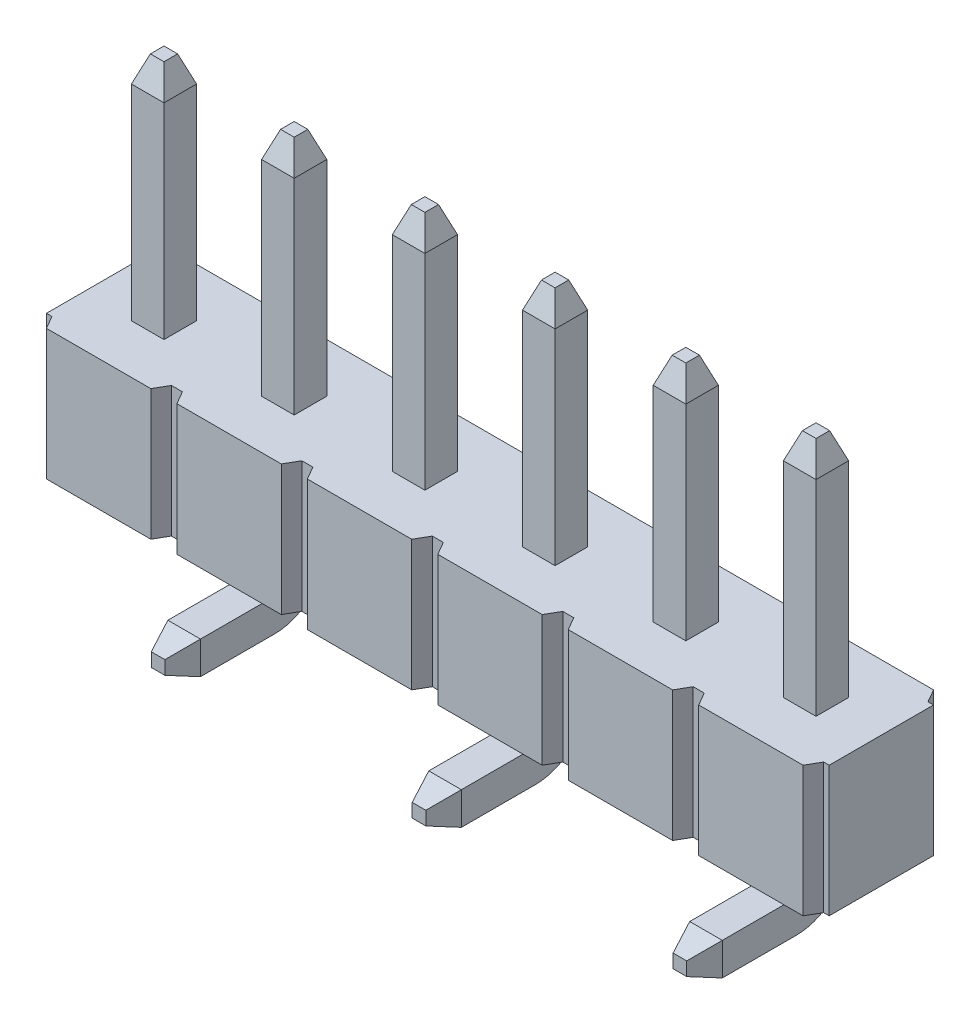
SolidWorks part; units mm, degrees
note: '?' marks a value the reader was unsure of.
ref_plane "Front" through (0, 0, 0) normal (0, 0, 1) x (1, 0, 0)
ref_plane "Top" through (0, 0, 0) normal (0, 1, 0) x (1, 0, 0)
ref_plane "Side" through (0, 0, 0) normal (1, 0, 0) x (0, 0, -1)
ref_plane "Plane for Single Option" through (2.54, 0, 0) normal (1, 0, 0) x (0, 0, -1)
ref_plane "Mid Plane" through (6.35, 0, 0) normal (1, 0, 0) x (0, 0, -1)
ref_axis "V Axis" through (0, -1.3049, 0) along (0, 1, 0)?
ref_axis "H Axis" through (0, 0, -2.8674) along (0, 0, 1)?
sketch "Sketch1" plane through (0, 0, 0) normal (0, 1, 0) x (1, 0, 0)
  line L0 (-1.27, 1.27) -> (1.27, 1.27) construction
  line L1 (-1.27, 1.27) -> (-1.27, -1.27) construction
  line L2 (1.27, -1.27) -> (-1.27, -1.27) construction
  line L3 (1.27, -1.27) -> (1.27, 1.27) construction
  line L4 (-1.27, -1.27) -> (1.27, 1.27) construction
  line L5 (-1.27, 1.27) -> (13.97, 1.27)
  line L6 (-1.27, 1.27) -> (-1.27, -1.27)
  line L7 (-1.27, -1.27) -> (13.97, -1.27)
  line L8 (13.97, -1.27) -> (13.97, 1.27)
  line L9 (1.0795, -1.27) -> (-1.0795, -1.27) construction
  line L10 (1.0795, -1.27) -> (1.0795, 1.27) construction
  dimension "D1" = 2.54
  dimension "D2" = 2.54
  dimension "D3" = 0.1905
  dimension "D4" = 15.24
extrude "Base Extrude" add sketch "Sketch1" along normal mid plane 2.54
sketch "Sketch8" plane through (0, 0, 0) normal (1, 0, 0) x (0, 0, -1)
  line L0 (-1.27, 1.27) -> (1.27, 1.27) construction
  line L1 (0.32, -1.087) -> (0.32, 5.262)
  line L3 (-0.315, -1.214) -> (-0.315, 5.262)
  line L4 (0.828, -1.595) -> (2.142, -1.595)
  line L5 (0.0025, 0) -> (0.0025, 0.5566) construction
  line L6 (-0.315, 5.262) -> (-0.1301, 5.77)
  line L7 (-0.1301, 5.77) -> (0.1351, 5.77)
  line L8 (0.1351, 5.77) -> (0.32, 5.262)
  line L9 (-0.315, 5.262) -> (0.32, 5.262) construction
  line L13 (0, -1.3049) -> (0, 1.3051) construction
  line L18 (0.701, -2.23) -> (2.142, -2.23)
  line L19 (2.65, -2.0451) -> (2.65, -1.7799)
  line L20 (3.683, -1.9125) -> (3.2473, -1.9125) construction
  line L24 (2.142, -1.595) -> (2.65, -1.7799)
  line L25 (2.142, -1.595) -> (2.142, -2.23) construction
  line L26 (2.142, -2.23) -> (2.65, -2.0451)
  arc A0 (-0.315, -1.214) -> (0.701, -2.23) centre (0.701, -1.214) ccw
  arc A1 (0.32, -1.087) -> (0.828, -1.595) centre (0.828, -1.087) ccw
  dimension "D10" = 1.016
  dimension "D11" = 0.508
  dimension "D1" = 0.508
  dimension "D2" = 70
  dimension "D3" = 4.5
  dimension "D4" = 0.0025
  dimension "D5" = 0.635
  dimension "D6" = 3.5
  dimension "D8" = 0.508
  dimension "D9" = 70
  dimension "Pin" = 2.65
extrude "Pin" add sketch "Sketch8" along normal mid plane 0.635
chamfer "Pin Chamfer" distance 0.508 angle 20 12 edges at (0.3175, -2.1376, -2.396) (0.3175, -1.9125, -2.65) (0.3175, -1.6874, -2.396) (-0.3175, 5.516, -0.2276) (-0.3175, 5.77, -0.0025) (-0.3175, 5.516, 0.2225) (-0.3175, -2.1376, -2.396) (-0.3175, -1.9125, -2.65) (-0.3175, -1.6874, -2.396) (0.3175, 5.516, -0.2276) (0.3175, 5.77, -0.0025) (0.3175, 5.516, 0.2225)
pattern_linear "Pin Pattern" count 3 spacing 5.08 along (1, 0, 0) of "Pin", "Pin Chamfer"
sketch "Sketch9" plane through (2.54, 0, 0) normal (1, 0, 0) x (0, 0, -1)
  line L1 (-0.32, -1.087) -> (-0.32, 5.262)
  line L3 (0.315, -1.214) -> (0.315, 5.262)
  line L4 (-0.32, 5.262) -> (0.315, 5.262) construction
  line L6 (0, -1.3049) -> (0, 1.3051) construction
  line L7 (-1.27, 1.27) -> (1.27, 1.27) construction
  line L8 (-0.0025, 0) -> (-0.0025, 1.0301) construction
  line L10 (-0.32, 5.262) -> (-0.1351, 5.77)
  line L11 (-0.1351, 5.77) -> (0.1301, 5.77)
  line L12 (0.1301, 5.77) -> (0.315, 5.262)
  line L18 (-0.701, -2.23) -> (-2.1445, -2.23)
  line L19 (-0.828, -1.595) -> (-2.1445, -1.595)
  line L20 (-2.1445, -1.595) -> (-2.6525, -1.7799)
  line L21 (-2.6525, -1.7799) -> (-2.6525, -2.0451)
  line L22 (-2.6525, -2.0451) -> (-2.1445, -2.23)
  line L23 (-2.1445, -1.595) -> (-2.1445, -2.23) construction
  line L24 (-2.6525, -1.9125) -> (-5.1592, -1.9125) construction
  arc A0 (-0.32, -1.087) -> (-0.828, -1.595) centre (-0.828, -1.087) cw
  arc A1 (0.315, -1.214) -> (-0.701, -2.23) centre (-0.701, -1.214) cw
  dimension "D10" = 0.508
  dimension "D11" = 1.016
  dimension "D1" = 0.0025
  dimension "D2" = 0.635
  dimension "D3" = 4.5
  dimension "D4" = 0.508
  dimension "D5" = 0.508
  dimension "D6" = 70
  dimension "D7" = 70
  dimension "D8" = 3.5
  dimension "D9" = 2.65
extrude "Pin 2" add sketch "Sketch9" along normal mid plane 0.635
chamfer "Pin 2 Chamfer" distance 0.508 angle 20 12 edges at (2.8575, -1.6874, 2.3985) (2.8575, -1.9125, 2.6525) (2.8575, -2.1376, 2.3985) (2.2225, 5.516, 0.2276) (2.2225, -1.6874, 2.3985) (2.2225, -1.9125, 2.6525) (2.2225, -2.1376, 2.3985) (2.2225, 5.516, -0.2225) (2.2225, 5.77, 0.0025) (2.8575, 5.516, -0.2225) (2.8575, 5.77, 0.0025) (2.8575, 5.516, 0.2276)
pattern_linear "Pin 2 Pattern" count 3 spacing 5.08 along (1, 0, 0) of "Pin 2", "Pin 2 Chamfer"
sketch "Sketch15" plane through (0, 1.27, 0) normal (0, 1, 0) x (-1, 0, 0)
  line L0 (-3.556, 1.27) -> (-3.7026, 1.016)
  line L1 (-3.9174, 1.016) -> (-4.064, 1.27)
  line L2 (-4.064, -1.27) -> (-3.9174, -1.016)
  line L3 (-3.7026, 1.016) -> (-3.9174, 1.016)
  line L4 (-3.9174, -1.016) -> (-3.7026, -1.016)
  line L5 (-3.7026, -1.016) -> (-3.556, -1.27)
  line L6 (-4.064, 1.27) -> (-3.556, 1.27)
  line L7 (-4.064, -1.27) -> (-3.556, -1.27)
  line L8 (-3.81, -1.27) -> (-3.81, 1.27) construction
  line L9 (1.27, -1.27) -> (1.27, 1.27) construction
  line L10 (1.27, 1.27) -> (-13.97, 1.27) construction
  line L11 (1.27, -1.27) -> (-13.97, -1.27) construction
  dimension "D1" = 5.08
  dimension "D2" = 0.254
  dimension "D3" = 0.254
  dimension "D4" = 60
  dimension "D5" = 60
  dimension "D6" = 0.2147
extrude "SV Cut" cut sketch "Sketch15" against normal through all
pattern_linear "SV Cut Pattern" count 5 spacing 2.54 along (1, 0, 0) of "SV Cut"
ref_plane "Polarize Plane -S" through (2.54, 0, 0) normal (1, 0, 0) x (0, 0, -1)
ref_plane "Polarize Plane -D" through (2.54, 0, 0) normal (1, 0, 0) x (0, 0, -1)
ref_plane "Polarize Plane-H" through (2.54, 0, 0) normal (1, 0, 0) x (0, 0, -1)
ref_plane "Polarize Plane-HD" through (2.54, 0, 0) normal (1, 0, 0) x (0, 0, -1)
pattern_linear "LPattern1" count 3 spacing 2.54 along (-1, 0, 0) of "SV Cut"
